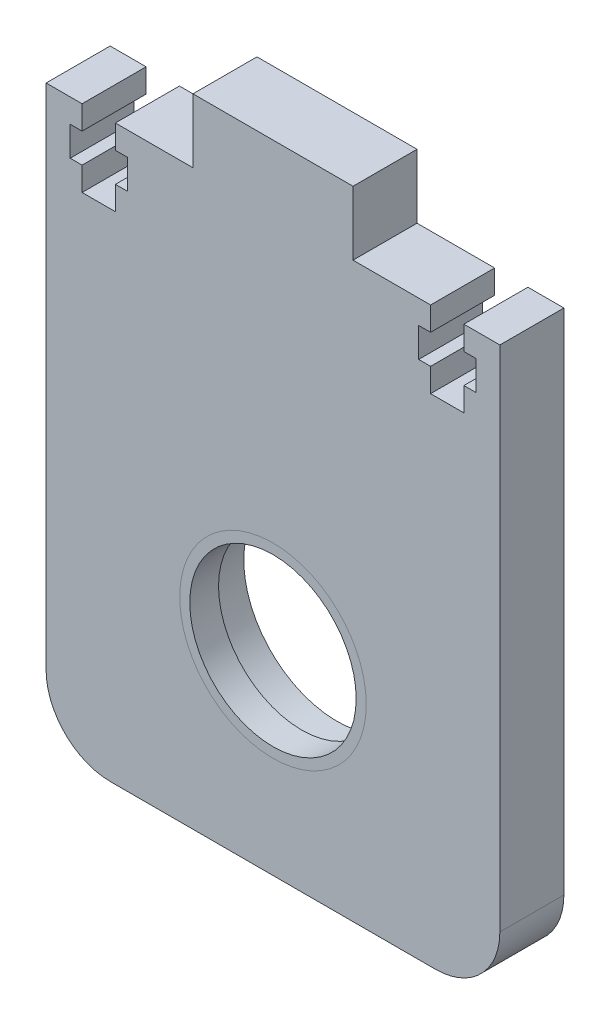
SolidWorks part; units mm, degrees
ref_plane "Front Plane" through (0, 0, 0) normal (0, 0, 1) x (1, 0, 0)
ref_plane "Top Plane" through (0, 0, 0) normal (0, 1, 0) x (1, 0, 0)
ref_plane "Right Plane" through (0, 0, 0) normal (1, 0, 0) x (0, 0, -1)
sketch "Sketch12" plane through (0, 0, 0) normal (0, 0, 1) x (1, 0, 0)
  line L0 (62.1258, 0) -> (62.1258, 113.63)
  line L1 (62.1258, 113.63) -> (152.1258, 113.63)
  line L2 (62.1258, 0) -> (152.1258, 0)
  line L3 (152.1258, 113.63) -> (152.1258, 0)
  circle A0 centre (99.6258, 37.5) radius 25.4
  circle A1 centre (99.6258, 37.5) radius 6.5
  dimension "D3" = 50.8
  dimension "D4" = 13
  dimension "D1" = 113.63
  dimension "D2" = 90
extrude "Boss-Extrude10" add sketch "Sketch12" along normal blind 12.7 separate body contours L1 L3 L2 L0
sketch "Sketch15" plane through (0, 0, 12.7) normal (0, 0, 1) x (1, 0, 0)
  line L0 (62.1258, 0) -> (152.1258, 0) construction
  circle A0 centre (107.1258, 38.6276) radius 25.4
  point P7 (107.1258, 0)
  dimension "D1" = 50.8
  dimension "D2" = 38.6276
sketch "Sketch24" plane through (0, 0, 12.7) normal (0, 0, 1) x (1, 0, 0)
  line L0 (62.1258, 113.63) -> (62.1258, 109.63)
  line L1 (62.1258, 0) -> (62.1258, 113.63) construction
  line L2 (62.1258, 109.63) -> (152.1258, 109.63)
  line L3 (152.1258, 113.63) -> (152.1258, 0) construction
  line L4 (152.1258, 109.63) -> (152.1258, 113.63)
  line L5 (152.1258, 113.63) -> (62.1258, 113.63)
  dimension "D1" = 4
sketch "Sketch25" plane through (0, 0, 12.7) normal (0, 0, 1) x (1, 0, 0)
  circle A0 centre (107.1258, 38.6276) radius 18.5
  dimension "D1" = 37
extrude "Cut-Extrude1" cut sketch "Sketch25" against normal through all
sketch "Sketch26" plane through (0, 0, 12.7) normal (0, 0, 1) x (1, 0, 0)
  circle A0 centre (107.1258, 38.6276) radius 16.5
  circle A1 centre (107.1258, 38.6276) radius 18.5
  dimension "D1" = 37
  dimension "D2" = 2
extrude "Boss-Extrude15" add sketch "Sketch26" against normal blind 5.7 separate body
fillet "Fillet1" radius 12.8 2 edges at (152.1258, 0, 6.35) (62.1258, 0, 6.35)
sketch "Sketch27" plane through (0, 0, 0) normal (0, 0, -1) x (-1, 0, 0)
  line L0 (-69.2638, 113.63) -> (-69.2638, 108.931)
  line L1 (-152.1258, 113.63) -> (-62.1258, 113.63) construction
  line L2 (-69.2638, 108.931) -> (-66.9018, 108.931)
  line L3 (-66.9018, 108.931) -> (-66.9018, 103.089)
  line L4 (-66.9018, 103.089) -> (-69.2638, 103.089)
  line L5 (-69.2638, 103.089) -> (-69.2638, 98.39)
  line L6 (-69.2638, 98.39) -> (-75.8678, 98.39)
  line L7 (-75.8678, 98.39) -> (-75.8678, 103.089)
  line L8 (-75.8678, 103.089) -> (-78.2298, 103.089)
  line L9 (-78.2298, 103.089) -> (-78.2298, 108.931)
  line L10 (-78.2298, 108.931) -> (-75.8678, 108.931)
  line L11 (-75.8678, 108.931) -> (-75.8678, 113.63)
  line L12 (-75.8678, 113.63) -> (-69.2638, 113.63)
  line L13 (-138.3838, 108.931) -> (-138.3838, 113.63)
  line L15 (-107.1258, 113.63) -> (-107.1258, 67.3255)
  line L28 (-136.0218, 108.931) -> (-138.3838, 108.931)
  line L29 (-136.0218, 103.089) -> (-136.0218, 108.931)
  line L30 (-138.3838, 103.089) -> (-136.0218, 103.089)
  line L31 (-138.3838, 98.39) -> (-138.3838, 103.089)
  line L32 (-144.9878, 98.39) -> (-138.3838, 98.39)
  line L33 (-144.9878, 103.089) -> (-144.9878, 98.39)
  line L34 (-147.3498, 103.089) -> (-144.9878, 103.089)
  line L35 (-147.3498, 108.931) -> (-147.3498, 103.089)
  line L36 (-144.9878, 108.931) -> (-147.3498, 108.931)
  line L37 (-144.9878, 113.63) -> (-144.9878, 108.931)
  line L38 (-138.3838, 113.63) -> (-144.9878, 113.63)
  point P22 (-72.5658, 113.63)
  point P29 (-141.6858, 113.63)
  line M19 (-62.1258, 113.63) -> (-152.1258, 113.63)
  dimension "D1" = 6.604
  dimension "D2" = 11.328
  dimension "D3" = 5.842
  dimension "D4" = 15.24
  dimension "D5" = 69.12
ref_axis "Axis2" through (107.1258, 113.63, 0) along (0, -1, 0)
extrude "Cut-Extrude2" cut sketch "Sketch27" against normal through all contours L11 L10 L9 L8 L7 L6 L5 L4 L3 L2 L0 M19 | L37 L36 L35 L34 L33 L32 L31 L30 L29 L28 L13 M19 region at (141.6858, 106.01, 0) region at (72.5658, 106.01, 0)
sketch "Sketch28" plane through (0, 113.63, 0) normal (0, 1, 0) x (1, 0, 0)
  line L0 (107.1258, 0) -> (91.2508, 0)
  line L1 (75.8678, 0) -> (138.3838, 0) construction
  line L2 (91.2508, 0) -> (91.2508, -12.7)
  line L3 (81.7258, -12.7) -> (132.5258, -12.7) construction
  line L4 (91.2508, -12.7) -> (123.0008, -12.7)
  line L5 (123.0008, -12.7) -> (123.0008, 0)
  line L6 (123.0008, 0) -> (107.1258, 0)
  dimension "D1" = 31.75
extrude "Boss-Extrude16" add sketch "Sketch28" along normal blind 12.7
